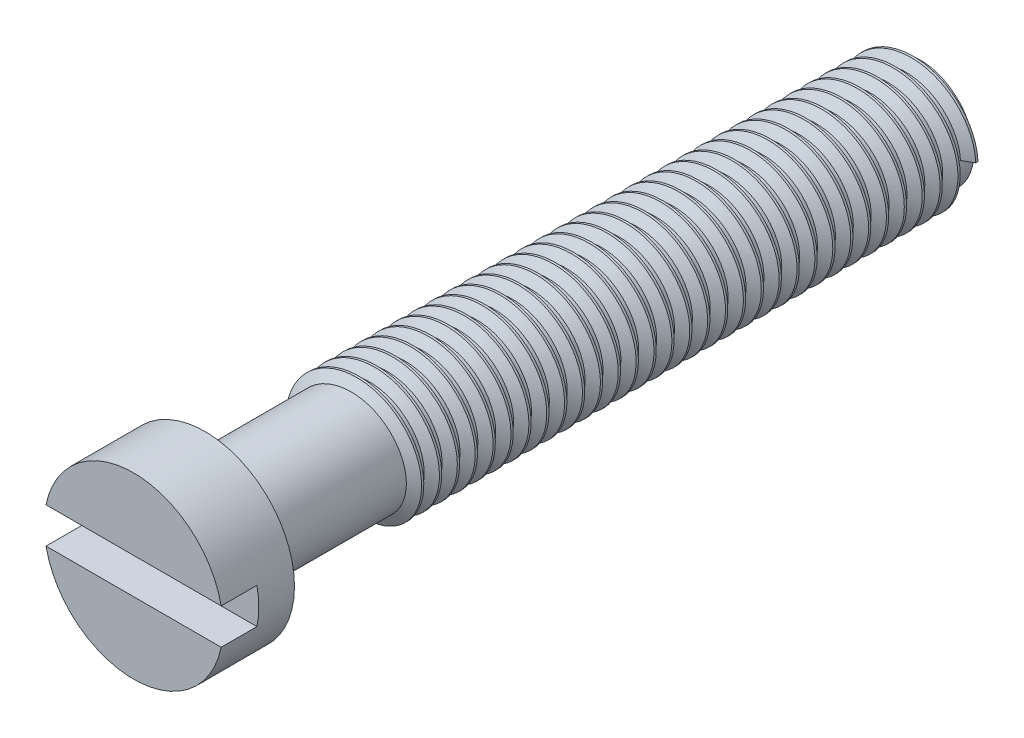
SolidWorks part; units mm, degrees
material "Alumina"
ref_plane "Front Plane" through (0, 0, 0) normal (0, 0, 1) x (1, 0, 0)
ref_plane "Top Plane" through (0, 0, 0) normal (0, 1, 0) x (1, 0, 0)
ref_plane "Right Plane" through (0, 0, 0) normal (1, 0, 0) x (0, 0, -1)
sketch "Sketch1" plane through (0, 0, 0) normal (0, 0, 1) x (1, 0, 0)
  circle A0 centre (0, 0) radius 1.5875
  dimension "D1" = 3.175
extrude "Boss-Extrude1" add sketch "Sketch1" along normal blind 1.27
sketch "Sketch2" plane through (0, 0, 1.27) normal (0, 0, 1) x (1, 0, 0)
  line L1 (-1.5875, 0.3175) -> (1.5875, 0.3175)
  line L2 (-1.5875, 0.3175) -> (-1.5875, -0.3175)
  line L3 (-1.5875, -0.3175) -> (1.5875, -0.3175)
  line L4 (1.5875, 0.3175) -> (1.5875, -0.3175)
  line L5 (-1.5875, 0.3175) -> (1.5875, -0.3175) construction
  line L6 (-1.5875, -0.3175) -> (1.5875, 0.3175) construction
  circle A0 centre (0, 0) radius 1.5875 construction
  point P0 (0, 0)
  point P6 (1.5875, 0)
  dimension "D1" = 0.635
extrude "Cut-Extrude1" cut sketch "Sketch2" against normal blind 0.635
sketch "Sketch3" plane through (0, 0, 0) normal (0, 0, -1) x (-1, 0, 0)
  circle A0 centre (0, 0) radius 0.9525
  dimension "D1" = 1.905
extrude "Boss-Extrude2" add sketch "Sketch3" along normal blind 12.7
thread "Thread1" pitch 0.3175 method extrude profile "Thread Profile1" start angle 0, offset 0, length 10, pitch 0.3175, diameter 1.905
ref_plane "Plane1" through (0.9525, 0, -12.7) normal (0, -1, 0) x (1, 0, 0)
sketch "Thread Profile1" plane through (0.9525, 0, -12.7) normal (0, -1, 0) x (1, 0, 0)
  line L0 (0, 0) -> (0, 0.3175) construction
  line L1 (0, 0) -> (0.1719, 0.0992)
  line L2 (0.1719, 0.0992) -> (0.1719, 0.1389)
  line L3 (0.1719, 0.1389) -> (0, 0.2381)
  line L4 (0.1719, 0.1191) -> (0, 0.1191) construction
  line L11 (0, 0) -> (0, 0.2381)
  point P2 (0, 0)
  dimension "Pitch" = 0.3175
  dimension "Profile_Angle" = 60
  dimension "Profile_Land" = 0.0397
  dimension "Profile_Height" = 0.1719
